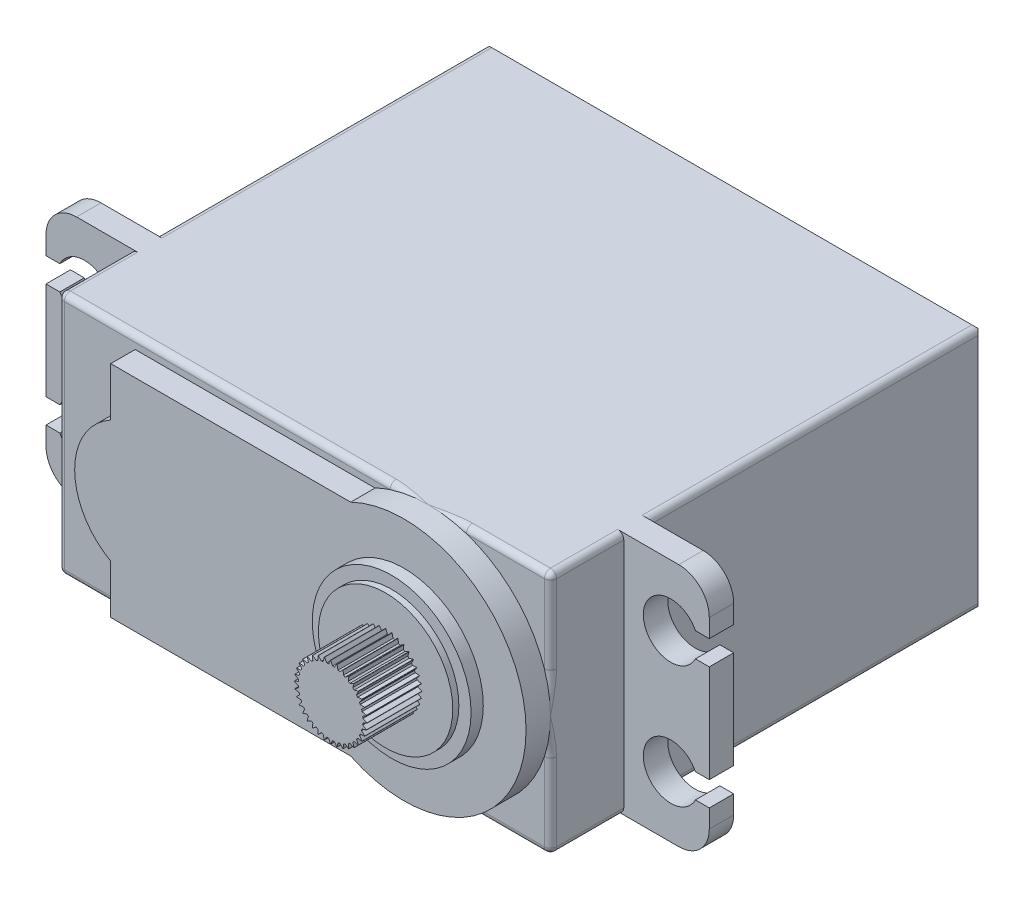
SolidWorks part; units mm, degrees
material "ABS"
ref_plane "Front Plane" through (0, 0, 0) normal (0, 0, 1) x (1, 0, 0)
ref_plane "Top Plane" through (0, 0, 0) normal (0, 1, 0) x (1, 0, 0)
ref_plane "Right Plane" through (0, 0, 0) normal (1, 0, 0) x (0, 0, -1)
sketch "Sketch1" plane through (0, 0, 0) normal (0, 0, 1) x (1, 0, 0)
  line L1 (-20.15, 10) -> (20.15, 10)
  line L2 (-20.15, 10) -> (-20.15, -10)
  line L3 (-20.15, -10) -> (20.15, -10)
  line L4 (20.15, 10) -> (20.15, -10)
  line L5 (-20.15, 10) -> (20.15, -10) construction
  line L6 (-20.15, -10) -> (20.15, 10) construction
  point P0 (0, 0)
  dimension "D1" = 40.3
  dimension "D2" = 20
extrude "Boss-Extrude1" add sketch "Sketch1" along normal blind 39
ref_plane "Plane1" through (0, 0, 29) normal (0, 0, 1) x (1, 0, 0)
sketch "Sketch2" plane through (0, 0, 29) normal (0, 0, 1) x (1, 0, 0)
  line L0 (24, 5) -> (24, -5) construction
  line L1 (-20.15, 10) -> (-27.15, 10)
  line L2 (-20.15, 10) -> (-20.15, -10)
  line L3 (-20.15, -10) -> (-27.15, -10)
  line L4 (-27.15, 10) -> (-27.15, 6)
  line L5 (20.15, 10) -> (27.15, 10)
  line L6 (20.15, 10) -> (20.15, -10)
  line L7 (20.15, -10) -> (27.15, -10)
  line L8 (27.15, 10) -> (27.15, 6)
  line L9 (-24, 5) -> (24, 5) construction
  line L10 (20.15, 10) -> (-20.15, 10) construction
  line L12 (-26.0156, 6) -> (-27.15, 6)
  line L14 (-26.0156, 4) -> (-27.15, 4)
  line L16 (-27.15, -6) -> (-27.15, -10)
  line L19 (26.0156, -6) -> (27.15, -6)
  line L20 (0, -11) -> (0, 11) construction
  line L21 (-26.0156, -6) -> (-27.15, -6)
  line L23 (26.0156, 4) -> (27.15, 4)
  line L24 (26.0156, 6) -> (27.15, 6)
  line L25 (-24, 5) -> (-24, -5) construction
  line L26 (-26.0156, -4) -> (-27.15, -4)
  line L30 (26.0156, -4) -> (27.15, -4)
  line L31 (26.0156, 4) -> (27.15, 4)
  line L32 (26.0156, 6) -> (27.15, 6)
  line L33 (27.15, 4) -> (27.15, -4)
  line L34 (27.15, -6) -> (27.15, -10)
  line L35 (-27.15, 4) -> (-27.15, -4)
  arc A0 (-26.0156, 4) -> (-26.0156, 6) centre (-24, 5) ccw
  arc A1 (-26.0156, -6) -> (-26.0156, -4) centre (-24, -5) ccw
  arc A2 (26.0156, 6) -> (26.0156, 4) centre (24, 5) ccw
  arc A3 (26.0156, -4) -> (26.0156, -6) centre (24, -5) ccw
  point P18 (24, 0)
  point P19 (20.15, 0)
  point P20 (0, 5)
  point P23 (0, 10)
  point P24 (-26.25, 5)
  point P32 (-26.25, -5)
  dimension "D3" = 4.5
  dimension "D7" = 2
  dimension "D1" = 7
  dimension "D2" = 7
  dimension "D4" = 10
  dimension "D5" = 48
  dimension "D6" = 2
  dimension "D8" = 20
  dimension "D9" = 20
extrude "Boss-Extrude2" add sketch "Sketch2" along normal blind 2 contours A3 L30 L33 L23 A2 L24 L8 L5 L6 L7 L34 L19 | A0 L12 L4 L1 L2 L3 L16 L21 A1 L26 L35 L14 region at (23.4305, 0, 29)
sketch "Sketch3" plane through (0, 0, 39) normal (0, 0, 1) x (1, 0, 0)
  line L0 (20.15, 10) -> (20.15, -10) construction
  line L1 (20.15, 10) -> (20.15, -10)
  line L2 (-13.85, -5.0029) -> (-13.85, -9)
  line L3 (-13.85, 9) -> (5.7911, 9)
  line L4 (-13.85, 9) -> (-13.85, 5.0029)
  line L5 (-13.85, -9) -> (5.7911, -9)
  line L7 (-13.85, 9) -> (18.4419, -5.5897) construction
  line L8 (-13.85, -9) -> (18.4419, 5.5897) construction
  line L9 (-20.15, -10) -> (20.15, -10) construction
  line L10 (20.15, 10) -> (-20.15, 10) construction
  line L11 (10.15, -10) -> (20.15, -10)
  line L12 (20.15, 10) -> (10.15, 10)
  arc A0 (5.7911, -9) -> (5.7911, 9) centre (10.15, 0) ccw
  arc A1 (-13.85, 5.0029) -> (-13.85, -5.0029) centre (-11.0882, 0) ccw
  point P4 (6.0701, 0)
  line M10 (20.15, 10) -> (-20.15, 10)
  line M11 (-20.15, 10) -> (-20.15, -10)
  line M12 (-20.15, -10) -> (20.15, -10)
  dimension "D1" = 18
  dimension "D2" = 34
extrude "Cut-Extrude1" cut sketch "Sketch3" against normal blind 2 contours A1 L4 L3 A0 L5 L2 M10 M11 M12 region at (7.9058, 9.7822, 39)
sketch "Sketch6" plane through (0, 0, 39) normal (0, 0, 1) x (1, 0, 0)
  line L7 (-13.85, -9) -> (5.7911, -9)
  line L8 (10.15, -10) -> (20.15, -10)
  line L9 (20.15, -10) -> (20.15, 10)
  line L10 (20.15, 10) -> (10.15, 10)
  line L11 (5.7911, 9) -> (-13.85, 9)
  line L12 (-13.85, 9) -> (-13.85, 5.0029)
  line L13 (-13.85, -5.0029) -> (-13.85, -9)
  line L15 (10.15, -10) -> (20.15, -10)
  line L16 (20.15, -10) -> (20.15, 10)
  line L17 (20.15, 10) -> (10.15, 10)
  arc A0 (5.7911, -9) -> (5.7911, 9) centre (10.15, 0) ccw construction
  arc A1 (10.15, -10) -> (10.15, 10) centre (10.15, 0) ccw
  arc A3 (5.7911, -9) -> (10.15, -10) centre (10.15, 0) ccw
  arc A4 (10.15, 10) -> (5.7911, 9) centre (10.15, 0) ccw
  arc A5 (-13.85, 5.0029) -> (-13.85, -5.0029) centre (-11.0882, 0) ccw
  line M13 (10.15, -10) -> (20.15, -10)
  line M14 (20.15, -10) -> (20.15, 10)
  line M15 (20.15, 10) -> (10.15, 10)
  dimension "D1" = 0
extrude "Cut-Extrude3" cut sketch "Sketch6" against normal blind 2 contours A1 L16 M15 | A1 M13 M14 region at (17.9163, -7.7663, 39) region at (17.9163, 7.7663, 39)
chamfer "Chamfer1" distance 2 angle 45 4 edges at (20.15, 0, 0) (0, 10, 0) (0, -10, 0) (-20.15, 0, 0)
fillet "Fillet1" radius 0.5 8 edges at (-20.15, 10, 34) (-20.15, 10, 15.5) (20.15, 10, 34) (20.15, 10, 15.5) (20.15, -10, 34) (20.15, -10, 15.5) (-20.15, -10, 34) (-20.15, -10, 15.5)
fillet "Fillet2" radius 0.5 11 edges at (-20.0036, 9.8536, 37) (20.0036, 9.8536, 37) (20.0036, -9.8536, 37) (-20.0036, -9.8536, 37) (20.15, 4.75, 37) (14.9, 10, 37) (-4.75, 10, 37) (20.15, -4.75, 37) (14.9, -10, 37) (-4.75, -10, 37) (-20.15, 0, 37)
sketch "Sketch7" plane through (0, 0, 39) normal (0, 0, 1) x (1, 0, 0)
  circle A0 centre (10.15, 0) radius 6.5
  circle A1 centre (10.15, 0) radius 3
  circle A2 centre (10.15, 0) radius 5.5
  dimension "D1" = 13
  dimension "D2" = 11
  dimension "D3" = 6
extrude "Boss-Extrude3" add sketch "Sketch7" along normal blind 1 contours A0 A2 region at (3.8338, 0, 39)
sketch "Sketch9" plane through (0, 0, 39) normal (0, 0, 1) x (1, 0, 0)
  circle A0 centre (10.15, 0) radius 5.5 construction
  circle A1 centre (10.15, 0) radius 3 construction
  circle A2 centre (10.15, 0) radius 5.5
  circle A3 centre (10.15, 0) radius 3
extrude "Boss-Extrude4" add sketch "Sketch9" along normal blind 1.5
sketch "Sketch10" plane through (0, 0, 39) normal (0, 0, 1) x (1, 0, 0)
  circle A0 centre (10.15, 0) radius 3 construction
  circle A1 centre (10.15, 0) radius 3
extrude "Boss-Extrude5" add sketch "Sketch10" along normal blind 6
sketch "Sketch11" plane through (0, 0, 0) normal (0, 0, -1) x (-1, 0, 0)
  line L0 (-18.15, 8) -> (-18.15, -8) construction
  line L1 (18.15, 8) -> (-18.15, 8) construction
  line L2 (-19.65, 10) -> (19.65, 10) construction
  line L3 (20.15, 9.5) -> (20.15, -9.5) construction
  line L4 (19.65, -10) -> (-19.65, -10) construction
  line L5 (-20.15, -9.5) -> (-20.15, 9.5) construction
  line L6 (-19.65, 10) -> (-15.15, 10)
  line L7 (20.15, 9.5) -> (20.15, 5)
  line L8 (19.65, -10) -> (15.15, -10)
  line L9 (-20.15, -9.5) -> (-20.15, -5)
  line L10 (-17.15, 5) -> (-20.15, 5)
  line L11 (-15.15, 7) -> (-15.15, 10)
  line L12 (24.75, 0) -> (-24.75, 0) construction
  line L13 (-15.15, -7) -> (-15.15, -10)
  line L14 (-17.15, -5) -> (-20.15, -5)
  line L15 (0, 11) -> (0, -11) construction
  line L16 (15.15, -7) -> (15.15, -10)
  line L17 (17.15, -5) -> (20.15, -5)
  line L18 (15.15, 7) -> (15.15, 10)
  line L19 (17.15, 5) -> (20.15, 5)
  line L20 (-15.15, -10) -> (-19.65, -10)
  line L21 (15.15, 10) -> (19.65, 10)
  line L22 (-20.15, 5) -> (-20.15, 9.5)
  line L23 (20.15, -5) -> (20.15, -9.5)
  arc A0 (-17.15, 5) -> (-15.15, 7) centre (-17.15, 7) ccw
  arc A1 (-20.15, -9.5) -> (-20.0036, -9.8536) centre (-19.65, -9.5) ccw construction
  arc A2 (-20.0036, -9.8536) -> (-19.65, -10) centre (-19.65, -9.5) ccw construction
  arc A3 (20.0036, 9.8536) -> (19.65, 10) centre (19.65, 9.5) ccw construction
  arc A4 (-19.65, 10) -> (-20.0036, 9.8536) centre (-19.65, 9.5) ccw construction
  arc A5 (-20.0036, 9.8536) -> (-20.15, 9.5) centre (-19.65, 9.5) ccw construction
  arc A6 (20.15, 9.5) -> (20.0036, 9.8536) centre (19.65, 9.5) ccw construction
  arc A7 (20.0036, -9.8536) -> (20.15, -9.5) centre (19.65, -9.5) ccw construction
  arc A8 (19.65, -10) -> (20.0036, -9.8536) centre (19.65, -9.5) ccw construction
  arc A9 (-20.15, -9.5) -> (-20.0036, -9.8536) centre (-19.65, -9.5) ccw
  arc A10 (-20.0036, -9.8536) -> (-19.65, -10) centre (-19.65, -9.5) ccw
  arc A11 (20.0036, 9.8536) -> (19.65, 10) centre (19.65, 9.5) ccw
  arc A12 (-19.65, 10) -> (-20.0036, 9.8536) centre (-19.65, 9.5) ccw
  arc A13 (-20.0036, 9.8536) -> (-20.15, 9.5) centre (-19.65, 9.5) ccw
  arc A14 (20.15, 9.5) -> (20.0036, 9.8536) centre (19.65, 9.5) ccw
  arc A15 (20.0036, -9.8536) -> (20.15, -9.5) centre (19.65, -9.5) ccw
  arc A16 (19.65, -10) -> (20.0036, -9.8536) centre (19.65, -9.5) ccw
  arc A17 (-17.15, -5) -> (-15.15, -7) centre (-17.15, -7) cw
  arc A18 (17.15, -5) -> (15.15, -7) centre (17.15, -7) ccw
  arc A19 (17.15, 5) -> (15.15, 7) centre (17.15, 7) cw
  dimension "D1" = 4
  dimension "D2" = 1
  dimension "D3" = 1
extrude "Cut-Extrude4" cut sketch "Sketch11" against normal blind 1.3
sketch "Sketch12" plane through (0, 0, 45) normal (0, 0, 1) x (1, 0, 0)
  line L1 (10.15, 3) -> (9.9957, 2.6393)
  line L2 (10.15, 3) -> (10.3043, 2.6393)
  line L5 (10.6709, 2.9544) -> (10.4564, 2.626)
  line L6 (10.6709, 2.9544) -> (10.7602, 2.5724)
  line L7 (11.1761, 2.8191) -> (10.9077, 2.5329)
  line L8 (11.1761, 2.8191) -> (11.1976, 2.4273)
  line L9 (11.65, 2.5981) -> (11.336, 2.3628)
  line L10 (11.65, 2.5981) -> (11.6032, 2.2085)
  line L11 (12.0784, 2.2981) -> (11.7283, 2.121)
  line L12 (12.0784, 2.2981) -> (11.9647, 1.9226)
  line L13 (12.4481, 1.9284) -> (12.0726, 1.8147)
  line L14 (12.4481, 1.9284) -> (12.271, 1.5783)
  line L15 (12.7481, 1.5) -> (12.3585, 1.4532)
  line L16 (12.7481, 1.5) -> (12.5128, 1.186)
  line L17 (12.9691, 1.0261) -> (12.5773, 1.0476)
  line L18 (12.9691, 1.0261) -> (12.6829, 0.7577)
  line L19 (13.1044, 0.5209) -> (12.7224, 0.6102)
  line L20 (13.1044, 0.5209) -> (12.776, 0.3064)
  line L21 (13.15, 0) -> (12.7893, 0.1543)
  line L22 (13.15, 0) -> (12.7893, -0.1543)
  line L23 (13.1044, -0.5209) -> (12.776, -0.3064)
  line L24 (13.1044, -0.5209) -> (12.7224, -0.6102)
  line L25 (12.9691, -1.0261) -> (12.6829, -0.7577)
  line L26 (12.9691, -1.0261) -> (12.5773, -1.0476)
  line L27 (12.7481, -1.5) -> (12.5128, -1.186)
  line L28 (12.7481, -1.5) -> (12.3585, -1.4532)
  line L29 (12.4481, -1.9284) -> (12.271, -1.5783)
  line L30 (12.4481, -1.9284) -> (12.0726, -1.8147)
  line L31 (12.0784, -2.2981) -> (11.9647, -1.9226)
  line L32 (12.0784, -2.2981) -> (11.7283, -2.121)
  line L33 (11.65, -2.5981) -> (11.6032, -2.2085)
  line L34 (11.65, -2.5981) -> (11.336, -2.3628)
  line L35 (11.1761, -2.8191) -> (11.1976, -2.4273)
  line L36 (11.1761, -2.8191) -> (10.9077, -2.5329)
  line L37 (10.6709, -2.9544) -> (10.7602, -2.5724)
  line L38 (10.6709, -2.9544) -> (10.4564, -2.626)
  line L39 (10.15, -3) -> (10.3043, -2.6393)
  line L40 (10.15, -3) -> (9.9957, -2.6393)
  line L41 (9.6291, -2.9544) -> (9.8436, -2.626)
  line L42 (9.6291, -2.9544) -> (9.5398, -2.5724)
  line L43 (9.1239, -2.8191) -> (9.3923, -2.5329)
  line L44 (9.1239, -2.8191) -> (9.1024, -2.4273)
  line L45 (8.65, -2.5981) -> (8.964, -2.3628)
  line L46 (8.65, -2.5981) -> (8.6968, -2.2085)
  line L47 (8.2216, -2.2981) -> (8.5717, -2.121)
  line L48 (8.2216, -2.2981) -> (8.3353, -1.9226)
  line L49 (7.8519, -1.9284) -> (8.2274, -1.8147)
  line L50 (7.8519, -1.9284) -> (8.029, -1.5783)
  line L51 (7.5519, -1.5) -> (7.9415, -1.4532)
  line L52 (7.5519, -1.5) -> (7.7872, -1.186)
  line L53 (7.3309, -1.0261) -> (7.7227, -1.0476)
  line L54 (7.3309, -1.0261) -> (7.6171, -0.7577)
  line L55 (7.1956, -0.5209) -> (7.5776, -0.6102)
  line L56 (7.1956, -0.5209) -> (7.524, -0.3064)
  line L57 (7.15, 0) -> (7.5107, -0.1543)
  line L58 (7.15, 0) -> (7.5107, 0.1543)
  line L59 (7.1956, 0.5209) -> (7.524, 0.3064)
  line L60 (7.1956, 0.5209) -> (7.5776, 0.6102)
  line L61 (7.3309, 1.0261) -> (7.6171, 0.7577)
  line L62 (7.3309, 1.0261) -> (7.7227, 1.0476)
  line L63 (7.5519, 1.5) -> (7.7872, 1.186)
  line L64 (7.5519, 1.5) -> (7.9415, 1.4532)
  line L65 (7.8519, 1.9284) -> (8.029, 1.5783)
  line L66 (7.8519, 1.9284) -> (8.2274, 1.8147)
  line L67 (8.2216, 2.2981) -> (8.3353, 1.9226)
  line L68 (8.2216, 2.2981) -> (8.5717, 2.121)
  line L69 (8.65, 2.5981) -> (8.6968, 2.2085)
  line L70 (8.65, 2.5981) -> (8.964, 2.3628)
  line L71 (9.1239, 2.8191) -> (9.1024, 2.4273)
  line L72 (9.1239, 2.8191) -> (9.3923, 2.5329)
  line L73 (9.6291, 2.9544) -> (9.5398, 2.5724)
  line L74 (9.6291, 2.9544) -> (9.8436, 2.626)
  circle A1 centre (10.15, 0) radius 3 construction
  circle A2 centre (10.15, 0) radius 3 construction
  arc A3 (7.5107, -0.1543) -> (7.524, -0.3064) centre (10.15, 0) ccw
  arc A4 (7.5776, -0.6102) -> (7.6171, -0.7577) centre (10.15, 0) ccw
  arc A5 (7.7227, -1.0476) -> (7.7872, -1.186) centre (10.15, 0) ccw
  arc A6 (7.9415, -1.4532) -> (8.029, -1.5783) centre (10.15, 0) ccw
  arc A7 (8.2274, -1.8147) -> (8.3353, -1.9226) centre (10.15, 0) ccw
  arc A8 (8.5717, -2.121) -> (8.6968, -2.2085) centre (10.15, 0) ccw
  arc A9 (8.964, -2.3628) -> (9.1024, -2.4273) centre (10.15, 0) ccw
  arc A10 (9.3923, -2.5329) -> (9.5398, -2.5724) centre (10.15, 0) ccw
  arc A11 (9.8436, -2.626) -> (9.9957, -2.6393) centre (10.15, 0) ccw
  arc A12 (10.3043, -2.6393) -> (10.4564, -2.626) centre (10.15, 0) ccw
  arc A13 (10.7602, -2.5724) -> (10.9077, -2.5329) centre (10.15, 0) ccw
  arc A14 (11.1976, -2.4273) -> (11.336, -2.3628) centre (10.15, 0) ccw
  arc A15 (11.6032, -2.2085) -> (11.7283, -2.121) centre (10.15, 0) ccw
  arc A16 (11.9647, -1.9226) -> (12.0726, -1.8147) centre (10.15, 0) ccw
  arc A17 (12.271, -1.5783) -> (12.3585, -1.4532) centre (10.15, 0) ccw
  arc A18 (12.5128, -1.186) -> (12.5773, -1.0476) centre (10.15, 0) ccw
  arc A19 (12.6829, -0.7577) -> (12.7224, -0.6102) centre (10.15, 0) ccw
  arc A20 (12.776, -0.3064) -> (12.7893, -0.1543) centre (10.15, 0) ccw
  arc A21 (12.7893, 0.1543) -> (12.776, 0.3064) centre (10.15, 0) ccw
  arc A22 (12.7224, 0.6102) -> (12.6829, 0.7577) centre (10.15, 0) ccw
  arc A23 (12.5773, 1.0476) -> (12.5128, 1.186) centre (10.15, 0) ccw
  arc A24 (12.3585, 1.4532) -> (12.271, 1.5783) centre (10.15, 0) ccw
  arc A25 (11.7283, 2.121) -> (11.6032, 2.2085) centre (10.15, 0) ccw
  arc A26 (11.336, 2.3628) -> (11.1976, 2.4273) centre (10.15, 0) ccw
  arc A27 (10.9077, 2.5329) -> (10.7602, 2.5724) centre (10.15, 0) ccw
  arc A28 (10.4564, 2.626) -> (10.3043, 2.6393) centre (10.15, 0) ccw
  arc A29 (9.9957, 2.6393) -> (9.8436, 2.626) centre (10.15, 0) ccw
  arc A30 (9.5398, 2.5724) -> (9.3923, 2.5329) centre (10.15, 0) ccw
  arc A31 (9.1024, 2.4273) -> (8.964, 2.3628) centre (10.15, 0) ccw
  arc A32 (8.6968, 2.2085) -> (8.5717, 2.121) centre (10.15, 0) ccw
  arc A33 (8.3353, 1.9226) -> (8.2274, 1.8147) centre (10.15, 0) ccw
  arc A34 (8.029, 1.5783) -> (7.9415, 1.4532) centre (10.15, 0) ccw
  arc A35 (7.7872, 1.186) -> (7.7227, 1.0476) centre (10.15, 0) ccw
  arc A36 (7.6171, 0.7577) -> (7.5776, 0.6102) centre (10.15, 0) ccw
  arc A37 (7.524, 0.3064) -> (7.5107, 0.1543) centre (10.15, 0) ccw
  arc A38 (12.0726, 1.8147) -> (11.9647, 1.9226) centre (10.15, 0) ccw
  dimension "D2" = 36
extrude "Cut-Extrude5" cut sketch "Sketch12" against normal up to surface (4.5 mm away) flip side to cut up to face at (15.65, 0, 40.5)
fillet "Fillet3" radius 0.015 36 edges at (7.1956, 0.5209, 42.75) (7.3309, 1.0261, 42.75) (7.5519, 1.5, 42.75) (7.8519, 1.9284, 42.75) (8.2216, 2.2981, 42.75) (8.65, 2.5981, 42.75) (9.1239, 2.8191, 42.75) (9.6291, 2.9544, 42.75) (10.15, 3, 42.75) (10.6709, 2.9544, 42.75) (11.1761, 2.8191, 42.75) (11.65, 2.5981, 42.75) (12.0784, 2.2981, 42.75) (12.4481, 1.9284, 42.75) (12.7481, 1.5, 42.75) (12.9691, 1.0261, 42.75) (13.1044, 0.5209, 42.75) (13.15, 0, 42.75) (13.1044, -0.5209, 42.75) (12.9691, -1.0261, 42.75) (12.7481, -1.5, 42.75) (12.4481, -1.9284, 42.75) (12.0784, -2.2981, 42.75) (11.65, -2.5981, 42.75) (11.1761, -2.8191, 42.75) (10.6709, -2.9544, 42.75) (10.15, -3, 42.75) (9.6291, -2.9544, 42.75) (9.1239, -2.8191, 42.75) (8.65, -2.5981, 42.75) (7.15, 0, 42.75) (7.1956, -0.5209, 42.75) (7.3309, -1.0261, 42.75) (7.5519, -1.5, 42.75) (7.8519, -1.9284, 42.75) (8.2216, -2.2981, 42.75)
fillet "Fillet4" radius 2.5 4 edges at (27.15, -10, 30) (27.15, 10, 30) (-27.15, -10, 30) (-27.15, 10, 30)
